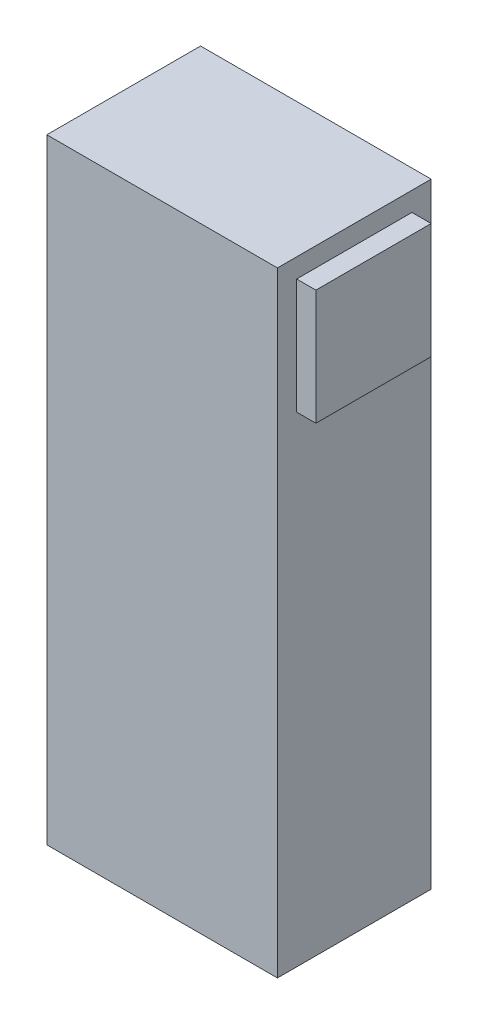
SolidWorks part; units mm, degrees
ref_plane "Front Plane" through (0, 0, 0) normal (0, 0, 1) x (1, 0, 0)
ref_plane "Top Plane" through (0, 0, 0) normal (0, 1, 0) x (1, 0, 0)
ref_plane "Right Plane" through (0, 0, 0) normal (1, 0, 0) x (0, 0, -1)
sketch "Sketch1" plane through (0, 0, 0) normal (0, 1, 0) x (1, 0, 0)
  line L1 (0, 0) -> (38.1, 0)
  line L2 (0, 0) -> (0, 25.4)
  line L3 (0, 25.4) -> (38.1, 25.4)
  line L4 (38.1, 0) -> (38.1, 25.4)
  dimension "D1" = 25.4
  dimension "D2" = 38.1
extrude "Boss-Extrude1" add sketch "Sketch1" along normal blind 101.6
sketch "Sketch2" plane through (38.1, 0, 0) normal (1, 0, 0) x (0, 0, -1)
  line L1 (3.175, 98.425) -> (22.225, 98.425)
  line L2 (3.175, 98.425) -> (3.175, 79.375)
  line L3 (3.175, 79.375) -> (22.225, 79.375)
  line L4 (0, 0) -> (25.4, 0)
  line L5 (25.4, 0) -> (25.4, 101.6)
  line L6 (25.4, 101.6) -> (0, 101.6)
  line L7 (0, 101.6) -> (0, 0)
  line L8 (0, 0) -> (25.4, 0)
  line L9 (25.4, 0) -> (25.4, 101.6)
  line L10 (25.4, 101.6) -> (0, 101.6)
  line L11 (0, 101.6) -> (0, 0)
  line L12 (22.225, 98.425) -> (22.225, 79.375)
  dimension "D2" = 3.175
  dimension "D3" = 3.175
  dimension "D4" = 3.175
  dimension "D1" = 0
extrude "Boss-Extrude2" add sketch "Sketch2" along normal blind 3.175 contours L12 L1 L2 L3 region at (38.1, 88.9, -12.7)
